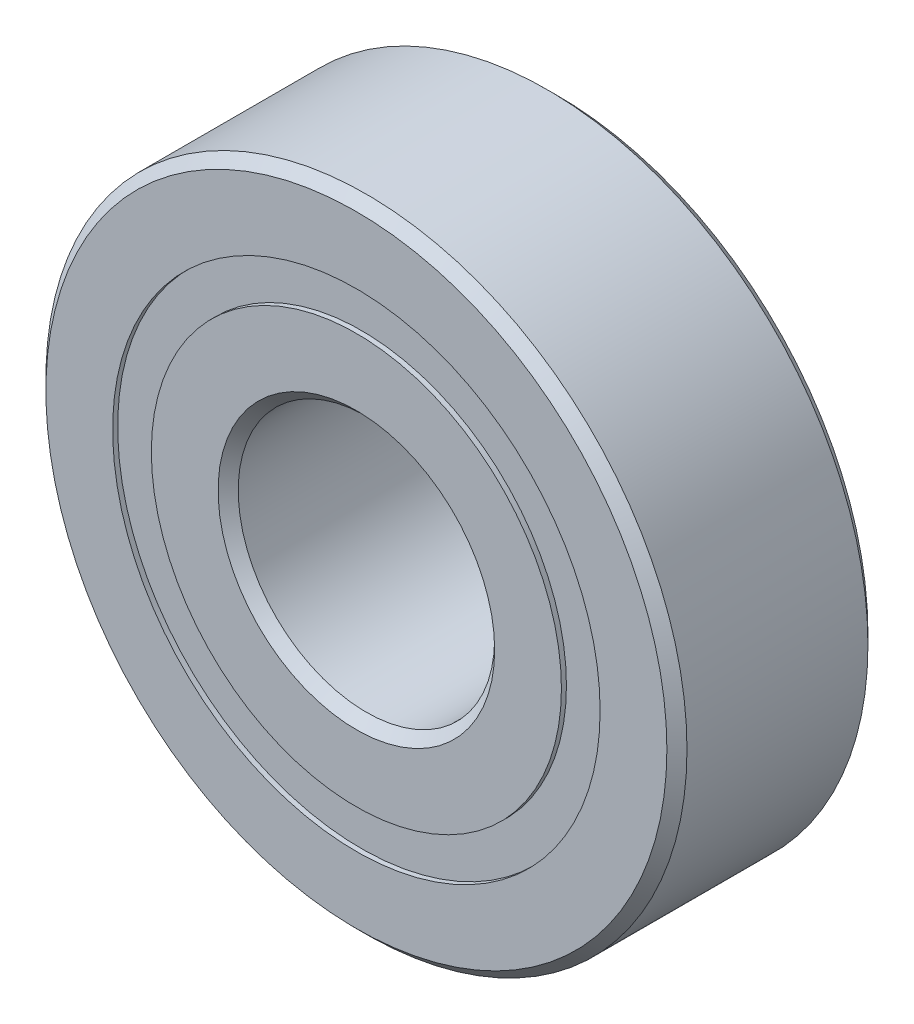
SolidWorks part; units mm, degrees
material "Chrome Stainless Steel"
ref_plane "Front Plane" through (0, 0, 0) normal (0, 0, 1) x (1, 0, 0)
ref_plane "Top Plane" through (0, 0, 0) normal (0, 1, 0) x (1, 0, 0)
ref_plane "Right Plane" through (0, 0, 0) normal (1, 0, 0) x (0, 0, -1)
sketch "Sketch1" plane through (0, 0, 0) normal (1, 0, 0) x (0, 0, -1)
  line L0 (-2.4892, 0) -> (2.4892, 0) construction
  line L1 (0, 7.9375) -> (0, -7.9375) construction
  line L2 (2.2403, 7.9375) -> (-2.2403, 7.9375)
  line L3 (-2.2403, 7.9375) -> (-2.4892, 7.6886)
  line L4 (-2.4892, 7.6886) -> (-2.4892, 6.0352)
  line L5 (-2.4892, 6.0352) -> (-1.1063, 6.0352)
  line L6 (2.4892, 6.0352) -> (1.1063, 6.0352)
  line L7 (2.4892, 7.6886) -> (2.4892, 6.0352)
  line L8 (2.2403, 7.9375) -> (2.4892, 7.6886)
  line L9 (0, 7.9375) -> (0, 5.5563) construction
  line L10 (0, 5.5563) -> (0, 3.175) construction
  arc A0 (-1.1063, 6.0352) -> (1.1063, 6.0352) centre (0, 5.5563) cw
  point P14 (0, 3.175)
  dimension "D3" = 2.2126
  dimension "D1" = 45
  dimension "Width" = 4.9784
  dimension "OD" = 15.875
  dimension "D2" = 0.2489
  dimension "Shaft Dia" = 6.35
  dimension "D4" = 0.479
revolve "Revolve1" add sketch "Sketch1" angle 360 about L0
sketch "Sketch3" plane through (0, 0, 0) normal (1, 0, 0) x (0, 0, -1)
  line L0 (-1.1063, 5.0773) -> (-2.4892, 5.0773)
  line L1 (-2.4892, 7.6886) -> (-2.4892, 6.0352) construction
  line L2 (-2.2403, 7.9375) -> (-2.4892, 7.6886) construction
  line L3 (-2.4892, 5.0773) -> (-2.4892, 3.4239)
  line L5 (-2.4892, 3.4239) -> (-2.2403, 3.175)
  line L6 (-2.2403, 3.175) -> (2.2403, 3.175)
  line L7 (2.2403, 7.9375) -> (2.2403, -7.9375) construction
  line L8 (2.2403, 3.175) -> (2.4892, 3.4239)
  line L9 (2.4892, -7.6886) -> (2.4892, 7.6886) construction
  line L10 (2.4892, 3.4239) -> (2.4892, 5.0773)
  line L11 (2.4892, 5.0773) -> (1.1063, 5.0773)
  line L12 (0, 7.9375) -> (0, -7.9375) construction
  line L13 (2.2403, 7.9375) -> (2.4892, 7.6886) construction
  arc A1 (1.1063, 5.0773) -> (-1.1063, 5.0773) centre (0, 5.5562) cw
  arc A2 (1.1063, 6.0352) -> (-1.1063, 6.0352) centre (0, 5.5563) ccw construction
revolve "Revolve3" add sketch "Sketch3" angle 360 about L0
sketch "Sketch4" plane through (0, 0, 0) normal (1, 0, 0) x (0, 0, -1)
  line L0 (-1.2055, 5.5563) -> (1.2055, 5.5563)
  arc A2 (-1.2055, 5.5563) -> (1.2055, 5.5563) centre (0, 5.5563) cw
  arc A3 (1.1063, 6.0352) -> (-1.1063, 6.0352) centre (0, 5.5563) ccw construction
revolve "Revolve4" add sketch "Sketch4" angle 360 about L0
ref_axis "Axis1" through (0, 0, -2.4892) along (0, 0, 1)
pattern_circular "CirPattern1" count 12 every 30 about axis through (0, 0, -2.4892) along (0, 0, 1) of bodies 104
sketch "Sketch5" plane through (0, 0, 0) normal (1, 0, 0) x (0, 0, -1)
  line L0 (-2.4892, 6.0352) -> (-1.1063, 6.0352) construction
  line L1 (-2.3647, 6.0352) -> (-1.2055, 6.0352)
  line L2 (-2.3647, 6.0352) -> (-2.3647, 5.0773)
  line L3 (-2.3647, 5.0773) -> (-1.2055, 5.0773)
  line L4 (-1.2055, 6.0352) -> (-1.2055, 5.0773)
  line L5 (-1.1063, 5.0773) -> (-2.4892, 5.0773) construction
  line L6 (2.4892, 6.0352) -> (1.1063, 6.0352) construction
  line L7 (2.3647, 6.0352) -> (1.2055, 6.0352)
  line L8 (2.3647, 6.0352) -> (2.3647, 5.0773)
  line L9 (2.3647, 5.0773) -> (1.2055, 5.0773)
  line L10 (1.2055, 6.0352) -> (1.2055, 5.0773)
  line L11 (2.4892, 5.0773) -> (1.1063, 5.0773) construction
  line L12 (-2.2403, 7.9375) -> (-2.4892, 7.6886) construction
  point P18 (-2.3647, 7.813)
revolve "Revolve5" add sketch "Sketch5" angle 360 about L0
ref_axis "Axis2" through (0, 0, -2.7381) along (0, 0, 1)
equation "\"D2@Sketch1\" = \"Width@Sketch1\"*.05"
equation "\"D3@Sketch1\" = \"Width@Sketch1\"/2.25"
equation "\"D4@Sketch1\" = (((\"OD@Sketch1\"-\"Width@Sketch1\")/2)/3.25)/3.5"
equation "\"D2@CirPattern1\" = 360/\"Balls@CirPattern1\""
